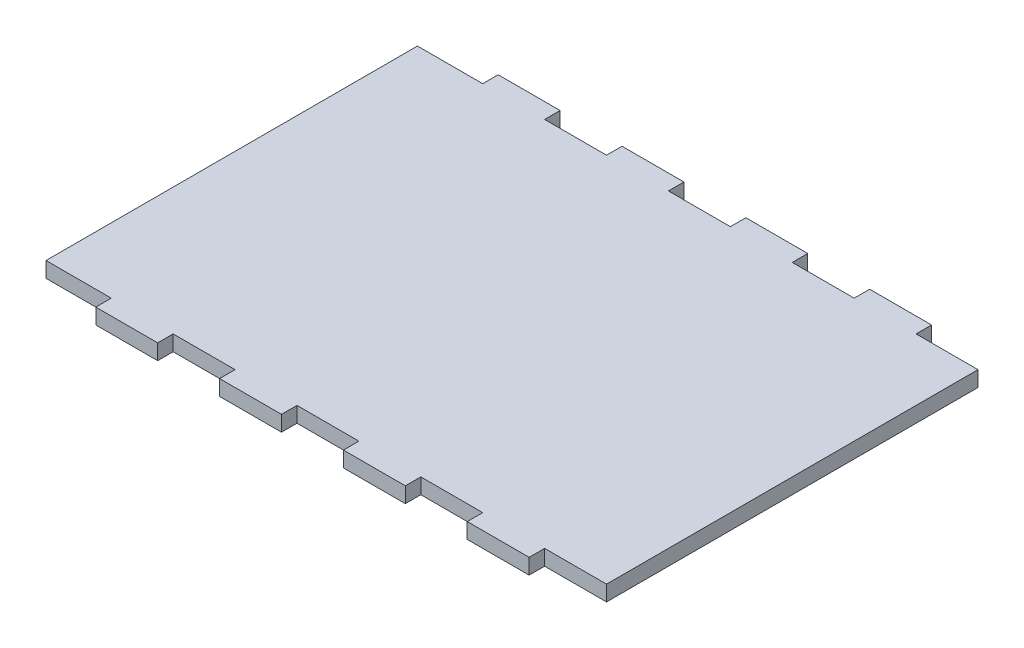
SolidWorks part; units mm, degrees
ref_plane "Front Plane" through (0, 0, 0) normal (0, 0, 1) x (1, 0, 0)
ref_plane "Top Plane" through (0, 0, 0) normal (0, 1, 0) x (1, 0, 0)
ref_plane "Right Plane" through (0, 0, 0) normal (1, 0, 0) x (0, 0, -1)
sketch "Sketch1" plane through (0, 0, 0) normal (0, 0, 1) x (1, 0, 0)
  line L0 (90.6195, -15.875) -> (90.6195, 155.575) construction
  line L1 (-139.3499, 155.575) -> (90.6195, 155.575)
  line L2 (-139.3499, 155.575) -> (-139.3499, 149.225)
  line L3 (-139.3499, 149.225) -> (90.6195, 149.225)
  line L4 (90.6195, 155.575) -> (90.6195, 149.225)
  dimension "D1" = 6.35
extrude "Boss-Extrude1" add sketch "Sketch1" along normal blind 152.4
sketch "Sketch2" plane through (0, 155.575, 0) normal (0, 1, 0) x (1, 0, 0)
  line L0 (65.2195, 0) -> (65.2195, 6.35)
  line L1 (90.6195, 0) -> (-139.3499, 0) construction
  line L2 (-139.3499, 6.35) -> (-112.5805, 6.35) construction
  line L3 (65.2195, 6.35) -> (39.8195, 6.35)
  line L4 (39.8195, 6.35) -> (39.8195, 0)
  line L5 (90.6195, 0) -> (65.2195, 0)
  line L6 (65.2195, 0) -> (39.8195, 0)
  line L9 (90.6195, 0) -> (-139.3499, 0)
  line L10 (-139.3499, 0) -> (-139.3499, -152.4)
  line L11 (-139.3499, -152.4) -> (90.6195, -152.4)
  line L12 (90.6195, -152.4) -> (90.6195, 0)
  line L13 (39.8195, 0) -> (-139.3499, 0)
  line L14 (-139.3499, 0) -> (-139.3499, -152.4)
  line L15 (-139.3499, -152.4) -> (90.6195, -152.4)
  line L16 (90.6195, -152.4) -> (90.6195, 0)
  line M7 (90.6195, 0) -> (-139.3499, 0)
  dimension "D1" = 25.4
  dimension "D2" = 25.4
  dimension "D3" = 0
extrude "Boss-Extrude2" add sketch "Sketch2" against normal blind 6.35 contours L3 L4 L0 M7 region at (52.5195, 155.575, -3.175)
pattern_linear "LPattern1" count 4 spacing 50.8 along (-1, 0, 0) of "Boss-Extrude2"
sketch "Sketch3" plane through (0, 0, 152.4) normal (0, 0, 1) x (1, 0, 0)
  line L0 (90.6195, 155.575) -> (-139.3499, 155.575) construction
  line L1 (65.2195, 155.575) -> (39.8195, 155.575)
  line L2 (65.2195, 155.575) -> (65.2195, 149.225)
  line L3 (65.2195, 149.225) -> (39.8195, 149.225)
  line L4 (39.8195, 155.575) -> (39.8195, 149.225)
  line L5 (-139.3499, 149.225) -> (90.6195, 149.225) construction
  dimension "D1" = 25.4
  dimension "D2" = 25.4
extrude "Boss-Extrude3" add sketch "Sketch3" along normal blind 6.35
pattern_linear "LPattern2" count 4 spacing 50.8 along (-1, 0, 0) of "Boss-Extrude3"
